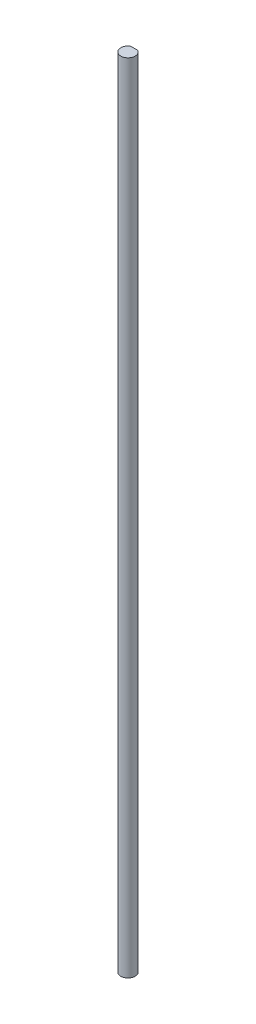
SolidWorks part; units mm, degrees
ref_plane "Front Plane" through (0, 0, 0) normal (0, 0, 1) x (1, 0, 0)
ref_plane "Top Plane" through (0, 0, 0) normal (0, 1, 0) x (1, 0, 0)
ref_plane "Right Plane" through (0, 0, 0) normal (1, 0, 0) x (0, 0, -1)
sketch "Sketch1" plane through (0, 0, 0) normal (0, 1, 0) x (1, 0, 0)
  line L0 (-1.5875, 2.7496) -> (1.5875, 2.7496)
  arc A0 (-1.5875, 2.7496) -> (1.5875, 2.7496) centre (0, 0) ccw
  dimension "D1" = 6.35
  dimension "D2" = 3.175
extrude "Boss-Extrude1" add sketch "Sketch1" along normal blind 350
